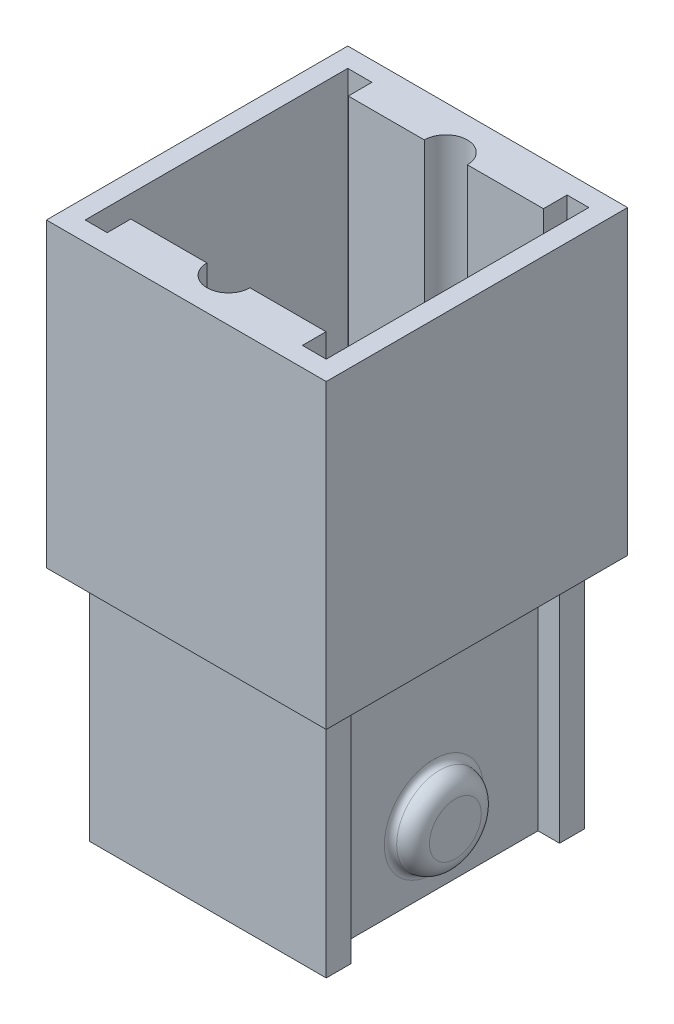
SolidWorks part; units mm, degrees
ref_plane "Front Plane" through (0, 0, 0) normal (0, 0, 1) x (1, 0, 0)
ref_plane "Top Plane" through (0, 0, 0) normal (0, 1, 0) x (1, 0, 0)
ref_plane "Right Plane" through (0, 0, 0) normal (1, 0, 0) x (0, 0, -1)
sketch "Sketch1" plane through (0, 0, 0) normal (0, 1, 0) x (1, 0, 0)
  line L1 (0, 0) -> (5.5, 0)
  line L2 (0, 0) -> (0, 6)
  line L3 (0, 6) -> (5.5, 6)
  line L4 (5.5, 0) -> (5.5, 6)
  dimension "D1" = 6
  dimension "D2" = 5.5
extrude "Boss-Extrude1" add sketch "Sketch1" along normal blind 12.5
sketch "Sketch2" plane through (0, 12.5, 0) normal (0, 1, 0) x (1, 0, 0)
  line L0 (0, 6) -> (0, 0) construction
  line L1 (0, 5.42) -> (0.5, 5.42)
  line L2 (0, 5.42) -> (0, 0.58)
  line L3 (0, 0.58) -> (0.5, 0.58)
  line L4 (0.5, 5.42) -> (0.5, 0.58)
  line L5 (5.5, 6) -> (0, 6) construction
  line L6 (0, 0) -> (5.5, 0) construction
  line L7 (5.5, 0) -> (5.5, 6) construction
  line L9 (5.5, 5.42) -> (5, 5.42)
  line L10 (5.5, 5.42) -> (5.5, 0.58)
  line L11 (5.5, 0.58) -> (5, 0.58)
  line L12 (5, 5.42) -> (5, 0.58)
  dimension "D1" = 0.5
  dimension "D2" = 0.58
  dimension "D3" = 0.58
  dimension "D4" = 0.5
  dimension "D5" = 0.58
  dimension "D6" = 0.58
extrude "Cut-Extrude1" cut sketch "Sketch2" against normal blind 12.5
sketch "Sketch3" plane through (5, 0, 0) normal (1, 0, 0) x (0, 0, -1)
  line L0 (5.42, 0) -> (0.58, 0) construction
  circle A0 centre (3, 1.5) radius 1
  dimension "D1" = 2
  dimension "D2" = 1.5
extrude "Boss-Extrude2" add sketch "Sketch3" along normal blind 0.5
fillet "Fillet1" radius 0.15 1 edges at (5, 1.5, -2)
fillet "Fillet2" radius 0.4 1 edges at (5.5, 1.5, -4)
sketch "Sketch4" plane through (0.5, 0, 0) normal (-1, 0, 0) x (0, 0, 1)
  line L0 (-0.58, 0) -> (-5.42, 0) construction
  circle A0 centre (-3.0171, 1.5) radius 1
  dimension "D1" = 1.5
  dimension "D2" = 2
extrude "Boss-Extrude3" add sketch "Sketch4" along normal blind 0.5
fillet "Fillet3" radius 0.1 1 edges at (0.5, 1.5, -4.0171)
fillet "Fillet4" radius 0.4 1 edges at (0, 1.5, -2.0171)
sketch "Sketch5" plane through (0, 12.5, 0) normal (0, 1, 0) x (1, 0, 0)
  line L0 (5.5, 6) -> (0, 6) construction
  line L1 (-0.5, 6.5) -> (6, 6.5)
  line L2 (-0.5, 6.5) -> (-0.5, -0.5)
  line L3 (-0.5, -0.5) -> (6, -0.5)
  line L4 (6, 6.5) -> (6, -0.5)
  line L5 (0, 6) -> (0, 5.42) construction
  line L6 (5.5, 0) -> (5.5, 0.58) construction
  line L7 (0, 0) -> (5.5, 0) construction
  dimension "D1" = 0.5
  dimension "D2" = 0.5
  dimension "D3" = 0.5
  dimension "D4" = 0.5
extrude "Boss-Extrude5" add sketch "Sketch5" against normal blind 7
sketch "Sketch7" plane through (0, 12.5, 0) normal (0, 1, 0) x (1, 0, 0)
  line L0 (-0.05, -0.05) -> (0.4617, -0.05)
  line L1 (0.4617, -0.05) -> (0.4617, 0.5)
  line L2 (0.4617, 0.5) -> (4.9957, 0.5)
  line L3 (4.9957, 0.5) -> (4.9957, -0.05)
  line L4 (4.9957, -0.05) -> (5.55, -0.05)
  line L5 (5.55, -0.05) -> (5.55, 6.05)
  line L6 (5.55, 6.05) -> (5.0457, 6.05)
  line L7 (5.0457, 6.05) -> (5.0457, 5.5)
  line L8 (5.0457, 5.5) -> (0.5117, 5.5)
  line L9 (0.5117, 5.5) -> (0.5117, 6.05)
  line L10 (0.5117, 6.05) -> (-0.05, 6.05)
  line L11 (-0.05, 6.05) -> (-0.05, -0.05)
  line L12 (6, 6.5) -> (-0.5, 6.5) construction
  line L14 (-0.5, 6.5) -> (-0.5, -0.5) construction
  line L15 (-0.5, -0.5) -> (6, -0.5) construction
  line L16 (6, -0.5) -> (6, 6.5) construction
  dimension "D1" = 0.45
  dimension "D2" = 0.45
  dimension "D3" = 0.45
  dimension "D4" = 0.55
  dimension "D5" = 0.45
  dimension "D6" = 0.45
  dimension "D7" = 0.45
  dimension "D8" = 0.55
extrude "Cut-Extrude4" cut sketch "Sketch7" against normal blind 6
sketch "Sketch8" plane through (0, 12.5, 0) normal (0, 1, 0) x (1, 0, 0)
  line L0 (5.0457, 5.5) -> (0.5117, 5.5) construction
  line L1 (0.4617, 0.5) -> (4.9957, 0.5) construction
  circle A0 centre (2.7787, 5.5) radius 0.5
  circle A1 centre (2.7287, 0.5) radius 0.5
extrude "Cut-Extrude5" cut sketch "Sketch8" against normal blind 6
